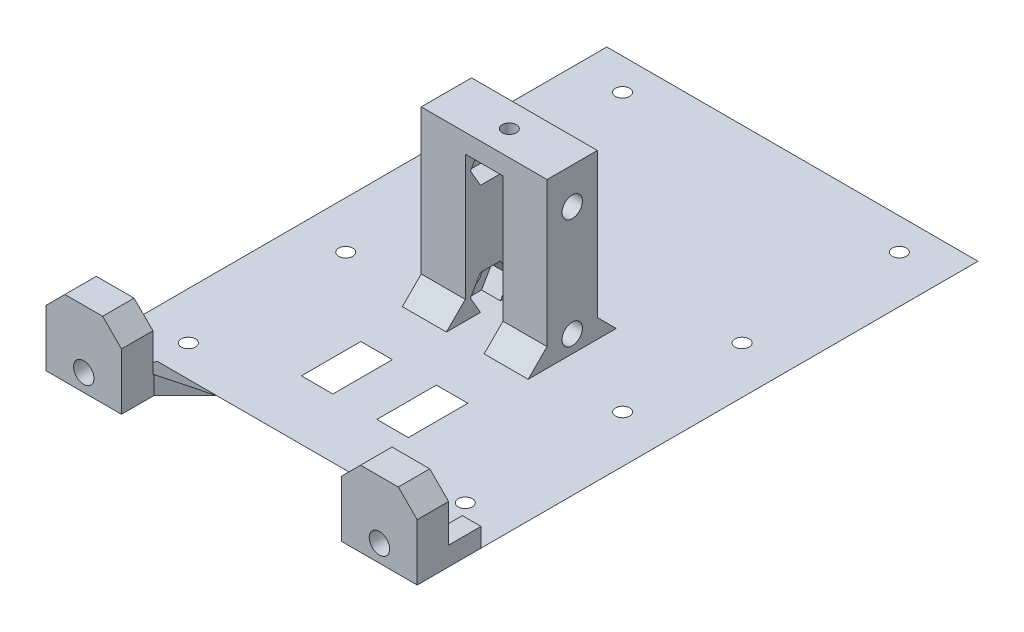
SolidWorks part; units mm, degrees
ref_plane "Alzado" through (0, 0, 0) normal (0, 0, 1) x (1, 0, 0)
ref_plane "Planta" through (0, 0, 0) normal (0, 1, 0) x (1, 0, 0)
ref_plane "Vista lateral" through (0, 0, 0) normal (1, 0, 0) x (0, 0, -1)
sketch "Croquis1" plane through (0, 0, 10.887) normal (0, 1, 0) x (1, 0, 0)
  line L0 (-29.5, 32.6406) -> (29.5, 32.6406)
  line L1 (29.5, 32.6406) -> (29.5, -47.3594)
  line L2 (29.5, -47.3594) -> (8.5, -47.3594)
  line L3 (8.5, -47.3594) -> (8.5, -27.4531)
  line L4 (8.5, -27.4531) -> (3.5, -27.4531)
  line L5 (3.5, -27.4531) -> (3.5, -47.3594)
  line L6 (3.5, -47.3594) -> (-3.5, -47.3594)
  line L7 (-3.5, -47.3594) -> (-3.5, -27.4531)
  line L8 (-3.5, -27.4531) -> (-8.5, -27.4531)
  line L9 (-8.5, -27.4531) -> (-8.5, -47.3594)
  line L10 (-8.5, -47.3594) -> (-29.5, -47.3594)
  line L11 (-29.5, -47.3594) -> (-29.5, 32.6406)
  line L12 (2, -7.3594) -> (47.9375, -7.3594) construction
  line L13 (0, 0) -> (0, 41.2344) construction
  dimension "D1" = 3.5
  dimension "D2" = 3.5
  dimension "D3" = 5
  dimension "D4" = 5
  dimension "D5" = 21
  dimension "D6" = 21
  dimension "D7" = 40
  dimension "D8" = 40
extrude "Base" add sketch "Croquis1" along normal blind 0.001
sketch "Sketch1" plane through (0, 0.001, 10.887) normal (0, 1, 0) x (1, 0, 0)
  line L0 (29.5, 32.6406) -> (-29.5, 32.6406) construction
  line L1 (-10, 23.1406) -> (10, 23.1406)
  line L2 (-10, 23.1406) -> (-10, 16.1406)
  line L3 (-10, 16.1406) -> (10, 16.1406)
  line L4 (10, 23.1406) -> (10, 16.1406)
  line L5 (-10, -8.3594) -> (10, -8.3594)
  line L6 (-10, -8.3594) -> (-10, -16.3594)
  line L7 (-10, -16.3594) -> (10, -16.3594)
  line L8 (10, -8.3594) -> (10, -16.3594)
  line L9 (0, 32.6406) -> (0, -23.7131) construction
  line L10 (8.5, -47.3594) -> (29.5, -47.3594) construction
  line L11 (3.5, -16.3594) -> (-3.5, -16.3594)
  line L12 (3.5, -16.3594) -> (3.5, -54.8594)
  line L13 (3.5, -54.8594) -> (-3.5, -54.8594)
  line L14 (-3.5, -16.3594) -> (-3.5, -54.8594)
  dimension "D1" = 9.5
  dimension "D2" = 7
  dimension "D3" = 10
  dimension "D4" = 10
  dimension "D5" = 24.5
  dimension "D6" = 8
  dimension "D7" = 10
  dimension "D8" = 10
  dimension "D9" = 7.5
extrude "Soporte Motores" add sketch "Sketch1" along normal blind 23 contours L9 L5 L6 L7 | L5 L9 L11 L7 L8 | L1 L9 L3 L4 | L9 L1 L2 L3 | L14 L13 L12 L11 region at (5, 0.001, 23.2464) region at (-5, 0.001, 23.2464) region at (-5, 0.001, -8.7536) region at (5, 0.001, -8.7536)
sketch "Sketch2" plane through (29.5, 0, 10.887) normal (1, 0, 0) x (0, 0, -1)
  line L0 (-54.8594, 23.001) -> (-46.3594, 0)
  line L1 (-47.3594, 0) -> (32.6406, 0) construction
  line L2 (-47.3594, 0) -> (-46.3594, 0)
  line L3 (-47.3594, 0) -> (-47.3594, 0.001)
  line L4 (-47.3594, 0.001) -> (-54.8594, 0.001)
  line L5 (-54.8594, 23.001) -> (-54.8594, 0.001)
  dimension "D1" = 1
extrude "Soporte Pala" cut sketch "Sketch2" against normal through all
sketch "Sketch3" plane through (-10, 0, 10.887) normal (-1, 0, 0) x (0, 0, 1)
  line L0 (8.3594, 0.001) -> (16.3594, 0.001) construction
  line L1 (16.3594, 23.001) -> (16.3594, 0.001) construction
  circle A0 centre (12.3594, 2.751) radius 1.625
  circle A1 centre (12.3594, 20.251) radius 1.625
  dimension "D1" = 3.25
  dimension "D2" = 3.25
  dimension "D3" = 2.75
  dimension "D4" = 4
  dimension "D5" = 17.5
extrude "Agujeros Motores" cut sketch "Sketch3" against normal through all
sketch "Sketch4" plane through (0, -15.4401, 51.5405) normal (0, -0.3466, 0.938) x (1, 0, 0)
  line L0 (-3.5, 16.4607) -> (3.5, 16.4607) construction
  circle A0 centre (0, 21.4607) radius 1
  circle A1 centre (0, 31.4607) radius 1
  dimension "D1" = 2
  dimension "D2" = 2
  dimension "D3" = 5
  dimension "D4" = 10
extrude "Agujeros pala" cut sketch "Sketch4" against normal blind 4
sketch "Croquis2" plane through (0, 0, -12.2536) normal (0, 0, -1) x (-1, 0, 0)
  line L0 (-10, 23.001) -> (-10, 0.001) construction
  line L1 (-5, 6) -> (-5, 0.001)
  line L2 (-5, 6) -> (-5, 18.001)
  line L3 (-5, 18.001) -> (5, 18.001)
  line L4 (5, 3.001) -> (5, 18.001)
  line L5 (10, 23.001) -> (10, 0.001) construction
  line L6 (10, 23.001) -> (-10, 23.001) construction
  line L7 (10, 0.001) -> (-10, 0.001) construction
  line L8 (5, 3.001) -> (5, 0.001)
  line L9 (5, 0.001) -> (-5, 0.001)
  dimension "D1" = 5
  dimension "D2" = 5
  dimension "D3" = 5
  dimension "D4" = 3
extrude "Hueco Soporte Posterior" cut sketch "Croquis2" against normal blind 10
sketch "Croquis3" plane through (-3.5, 0, 10.887) normal (-1, 0, 0) x (0, 0, 1)
  line L1 (21.9062, 0.001) -> (36.9062, 0.001)
  line L2 (21.9062, 23.001) -> (16.3594, 23.001)
  line L3 (21.9062, 23.001) -> (36.9062, 23.001)
  line L4 (36.9062, 0.001) -> (36.9062, 23.001)
  line L5 (16.3594, 23.001) -> (54.8594, 23.001) construction
  line L7 (16.3594, 23.001) -> (16.3594, 0.001)
  line L8 (16.3594, 0.001) -> (21.9062, 0.001)
  dimension "D1" = 15
extrude "Corte_Soporte_PALA_MOTOR" cut sketch "Croquis3" against normal up to next
sketch "Sketch5" plane through (-8.5, 0, 10.887) normal (1, 0, 0) x (0, 0, -1)
  line L0 (-36.9062, 0.001) -> (-36.9062, 0)
  line L1 (-46.3594, 0) -> (32.6406, 0) construction
  line L2 (-36.9062, 0) -> (-46.3594, 0)
  line L3 (-46.3594, 0) -> (-46.3597, 0.001)
  line L4 (-46.3597, 0.001) -> (-36.9062, 0.001)
extrude "Boss-Extrude2" add sketch "Sketch5" along normal blind 20
chamfer "Chamfer1" distance 3 angle 45 10 edges at (-3.5, 0.001, 52.52) (-7.5, 0.001, -5.2536) (-5, 0.001, -8.7536) (-7.5, 0.001, -12.2536) (7.5, 0.001, -12.2536) (5, 0.001, -8.7536) (7.5, 0.001, -5.2536) (0, 0.001, 19.2464) (3.5, 0.001, 52.52)
sketch "Croquis4" plane through (-29.5, 0, 10.887) normal (-1, 0, 0) x (0, 0, 1)
  line L0 (36.9062, 23.001) -> (36.9062, 0.001)
  line L1 (46.3594, 0) -> (46.3594, 0.001)
  line L2 (-32.6406, 0.001) -> (46.3597, 0.001) construction
  line L3 (46.3594, 0.001) -> (36.9062, 0.001)
  line L4 (46.3594, 0) -> (54.8594, 23.001)
  line L5 (54.8594, 23.001) -> (36.9062, 23.001)
extrude "Cortar-Extruir1" cut sketch "Croquis4" against normal through all both and the other way through all
sketch "Croquis5" plane through (-29.5, 0, 10.887) normal (-1, 0, 0) x (0, 0, 1)
  line L0 (46.3594, 0) -> (56.5036, 0)
  line L1 (56.5036, 0) -> (56.5036, 12)
  line L2 (56.5036, 12) -> (51.5036, 12)
  line L3 (51.5036, 12) -> (51.5036, 3.001)
  line L4 (51.5036, 3.001) -> (46.3594, 3)
  line L5 (46.3594, 0) -> (46.3594, 0.001) construction
  line L6 (-32.6406, 0.001) -> (46.3594, 0.001) construction
  line L7 (46.3594, 3) -> (46.3594, 0)
  dimension "D1" = 3
  dimension "D2" = 12
  dimension "D3" = 5
extrude "Saliente-Extruir1" add sketch "Croquis5" along normal blind 12 from vertex starting at point (29.5, 0.001, 57.2464)
sketch "Croquis6" plane through (-29.5, 0, 10.887) normal (-1, 0, 0) x (0, 0, 1)
  line L0 (46.3594, 0.001) -> (46.3594, 0)
  line L1 (46.3594, 0) -> (56.5036, 0)
  line L2 (56.5036, 0) -> (56.5036, 12)
  line L3 (56.5036, 12) -> (51.5036, 12)
  line L4 (51.5036, 12) -> (51.5036, 3.001)
  line L5 (51.5036, 3.001) -> (46.3594, 3) construction
  line L6 (51.5036, 12) -> (51.5036, 3.001) construction
  line L7 (51.5036, 3.001) -> (46.3594, 0.001)
extrude "Saliente-Extruir2" add sketch "Croquis6" against normal blind 12
chamfer "Chaflán1" distance 5 angle 45 2 edges at (-17.5, 0.0005, 57.2464) (17.5, 0.0005, 57.2464)
sketch "Croquis7" plane through (0, 0, 67.3906) normal (0, 0, 1) x (1, 0, 0)
  line L1 (0, 0) -> (0, 16.623) construction
  line L2 (-17.5, 0) -> (-29.5, 0) construction
  line L4 (12.5, 0.001) -> (-12.5, 0.001) construction
  circle A0 centre (-23.5, 2.751) radius 1.625
  circle A1 centre (23.5, 2.751) radius 1.625
  dimension "D1" = 3.25
  dimension "D3" = 47
  dimension "D4" = 2.751
  dimension "D2" = 2.75
extrude "Cortar-Extruir2" cut sketch "Croquis7" against normal blind 12
sketch "Croquis8" plane through (0, 0, 62.3906) normal (0, 0, -1) x (-1, 0, 0)
  line L1 (-21.9123, 0.001) -> (-20.3246, 2.751)
  line L2 (-20.3246, 2.751) -> (-21.9123, 5.501)
  line L3 (-21.9123, 5.501) -> (-25.0877, 5.501)
  line L4 (-25.0877, 5.501) -> (-26.6754, 2.751)
  line L5 (-26.6754, 2.751) -> (-25.0877, 0.001)
  line L6 (-25.0877, 0.001) -> (-21.9123, 0.001)
  line L7 (25.0877, 0.001) -> (26.6754, 2.751)
  line L8 (26.6754, 2.751) -> (25.0877, 5.501)
  line L9 (25.0877, 5.501) -> (21.9123, 5.501)
  line L10 (21.9123, 5.501) -> (20.3246, 2.751)
  line L11 (20.3246, 2.751) -> (21.9123, 0.001)
  line L12 (21.9123, 0.001) -> (25.0877, 0.001)
  circle A0 centre (-23.5, 2.751) radius 2.75 construction
  circle A1 centre (23.5, 2.751) radius 2.75 construction
  dimension "D1" = 5.5
extrude "Cortar-Extruir3" cut sketch "Croquis8" against normal blind 2.5 and the other way blind 15
sketch "Croquis10" plane through (-29.5, 0, 10.887) normal (-1, 0, 0) x (0, 0, 1)
  line L1 (-26.1406, 0.001) -> (-12.3855, 0.001)
  line L2 (-26.1406, 0.001) -> (-26.1406, 28.0148)
  line L3 (-26.1406, 28.0148) -> (-12.3855, 28.0148)
  line L4 (-12.3855, 0.001) -> (-12.3855, 28.0148)
extrude "Cortar-Extruir5" cut sketch "Croquis10" against normal through all both and the other way through all
sketch "Croquis11" plane through (-10, 0, 10.887) normal (-1, 0, 0) x (0, 0, 1)
  line L1 (8.3594, 23.001) -> (16.3594, 23.001)
  line L2 (8.3594, 23.001) -> (8.3594, 26.001)
  line L3 (8.3594, 26.001) -> (16.3594, 26.001)
  line L4 (16.3594, 23.001) -> (16.3594, 26.001)
  circle A0 centre (12.3594, 20.251) radius 1.625 construction
  dimension "D1" = 5.75
extrude "Saliente-Extruir3" add sketch "Croquis11" against normal up to vertex (20 mm away) up to point (10, 23.001, 19.2464)
sketch "Croquis12" plane through (0, 0, 19.2464) normal (0, 0, -1) x (-1, 0, 0)
  line L0 (-29.5, 0.001) -> (29.5, 0.001) construction
  line L1 (-3, 0.001) -> (3, 0.001)
  line L2 (-3, 0.001) -> (-3, 23.001)
  line L3 (-3, 23.001) -> (3, 23.001)
  line L4 (3, 0.001) -> (3, 23.001)
  line L5 (-10, 26.001) -> (10, 26.001) construction
  dimension "D1" = 3
  dimension "D2" = 6
  dimension "D3" = 3
extrude "Cortar-Extruir6" cut sketch "Croquis12" against normal up to vertex (11 mm away) from vertex up to point (-10, 0.001, 30.2464) starting at point (-10, 0.001, 16.2464)
sketch "Croquis13" plane through (3, 0, 10.887) normal (-1, 0, 0) x (0, 0, 1)
  line L1 (13.9471, 0.001) -> (15.5348, 2.751)
  line L2 (15.5348, 2.751) -> (13.9471, 5.501)
  line L3 (13.9471, 5.501) -> (10.7717, 5.501)
  line L4 (10.7717, 5.501) -> (9.1839, 2.751)
  line L5 (9.1839, 2.751) -> (10.7717, 0.001)
  line L6 (10.7717, 0.001) -> (13.9471, 0.001)
  line L7 (13.9471, 17.501) -> (15.5348, 20.251)
  line L8 (15.5348, 20.251) -> (13.9471, 23.001)
  line L9 (13.9471, 23.001) -> (10.7717, 23.001)
  line L10 (10.7717, 23.001) -> (9.1839, 20.251)
  line L11 (9.1839, 20.251) -> (10.7717, 17.501)
  line L12 (10.7717, 17.501) -> (13.9471, 17.501)
  circle A0 centre (12.3594, 2.751) radius 2.75 construction
  circle A1 centre (12.3594, 20.251) radius 2.75 construction
  dimension "D1" = 5.5
  dimension "D2" = 5.5
extrude "Cortar-Extruir7" cut sketch "Croquis13" against normal blind 3 and the other way blind 9
chamfer "Chaflán2" distance 3 angle 45 4 edges at (17.5, 12, 64.8906) (29.5, 12, 64.8906) (-17.5, 12, 64.8906) (-29.5, 12, 64.8906)
sketch "Croquis14" plane through (0, 0.001, 10.887) normal (0, 1, 0) x (1, 0, 0)
  line L4 (-10, -12.3594) -> (10, -12.3594) construction
  line L6 (-10, -5.3594) -> (-10, -19.3594) construction
  line L7 (10, -5.3594) -> (10, -19.3594) construction
  circle A2 centre (0, -42.3594) radius 3
  circle A3 centre (0, -42.3594) radius 1.125
  dimension "D1" = 30
  dimension "D4" = 2.25
  dimension "D5" = 6
sketch "Croquis15" plane through (0, 26.001, 10.887) normal (0, 1, 0) x (1, 0, 0)
  circle A0 centre (0, -12.3594) radius 1.125
  dimension "D1" = 2.25
extrude "Cortar-Extruir8" cut sketch "Croquis15" against normal up to next
sketch "Croquis16" plane through (0, 0.001, 10.887) normal (0, 1, 0) x (1, 0, 0)
  line L0 (-29.5, 32.6406) -> (-29.5, -46.3594) construction
  line L1 (-12.5, -46.3594) -> (-21.9123, -46.3594) construction
  line L2 (-22, -41.3594) -> (-22, 2.6406) construction
  circle A0 centre (-22, -41.3594) radius 1.125
  circle A1 centre (22, -41.3594) radius 1.125
  circle A2 centre (-22, 2.6406) radius 1.125
  circle A3 centre (22, 2.6406) radius 1.125
  circle A4 centre (-22, 27.6406) radius 1.125
  circle A5 centre (22, 27.6406) radius 1.125
  circle A6 centre (-22, -16.3594) radius 1.125
  circle A7 centre (22, -16.3594) radius 1.125
  dimension "D1" = 2.25
  dimension "D4" = 5
  dimension "D2" = 44
  dimension "D3" = 7.5
  dimension "D6" = 44
  dimension "D5" = 2
  dimension "D7" = 2
  dimension "D8" = 2
extrude "Cortar-Extruir9" cut sketch "Croquis16" against normal through all
ref_plane "Plano1" through (-29.5, 0, -21.7536) normal (0, 0, 1) x (1, 0, 0)
ref_plane "Plano4" through (-29.5, 0, 67.3906) normal (0, 0, 1) x (1, 0, 0)
sketch3d "Croquis3D1"
  point P0 (16.7297, 0.001, 46.1959)
